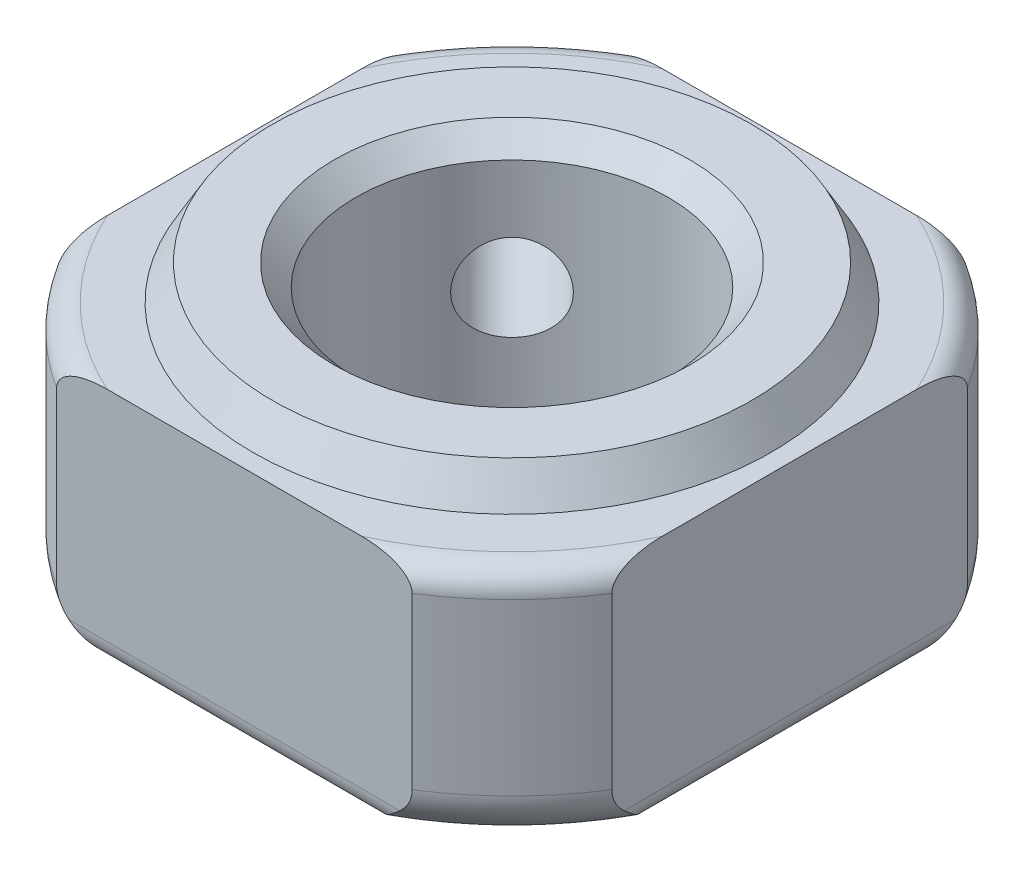
SolidWorks part; units mm, degrees
ref_plane "Front" through (0, 0, 0) normal (0, 0, 1) x (1, 0, 0)
ref_plane "Top" through (0, 0, 0) normal (0, 1, 0) x (1, 0, 0)
ref_plane "Right" through (0, 0, 0) normal (1, 0, 0) x (0, 0, -1)
sketch "Sketch1" plane through (0, 0, 0) normal (0, 1, 0) x (1, 0, 0)
  line L0 (-8, 5.1235) -> (-8, -5.1235)
  line L1 (-8, 8) -> (8, 8) construction
  line L2 (-8, 8) -> (-8, -8) construction
  line L3 (-8, -8) -> (8, -8) construction
  line L4 (8, 8) -> (8, -8) construction
  line L5 (-8, 8) -> (8, -8) construction
  line L6 (-8, -8) -> (8, 8) construction
  line L7 (-5.1235, -8) -> (5.1235, -8)
  line L8 (8, -5.1235) -> (8, 5.1235)
  line L9 (5.1235, 8) -> (-5.1235, 8)
  arc A0 (-5.1235, 8) -> (-8, 5.1235) centre (0, 0) ccw
  arc A1 (8, 5.1235) -> (5.1235, 8) centre (0, 0) ccw
  arc A2 (5.1235, -8) -> (8, -5.1235) centre (0, 0) ccw
  arc A3 (-8, -5.1235) -> (-5.1235, -8) centre (0, 0) ccw
  point P0 (0, 0)
  dimension "D2" = 19
  dimension "D1" = 16
extrude "Boss-Extrude1" add sketch "Sketch1" along normal blind 8
sketch "Sketch2" plane through (0, 0, 0) normal (0, 0, 1) x (1, 0, 0)
  line L0 (6.9, 8) -> (7.4774, 7)
  line L1 (-5.1235, 8) -> (5.1235, 8) construction
  line L2 (7.4774, 7) -> (9.7567, 7)
  line L4 (6.9, 8) -> (9.7567, 8)
  line L5 (9.7567, 8) -> (9.7567, 7)
  line L6 (0, 0) -> (0, 12.5902) construction
  dimension "D1" = 1
  dimension "D2" = 60
  dimension "D3" = 6.9
revolve "Cut-Revolve1" cut sketch "Sketch2" angle 360 about L6
hole_wizard "M10x1.0 Tapped Hole1" positions "Sketch3" profile "Sketch5" tap size "M10x1.0" standard "ISO" end condition up to next
sketch "Sketch3" plane through (0, 0, 0) normal (0, -1, 0) x (-1, 0, 0)
  point P0 (0, 0)
sketch "Sketch5" plane through (0, 0, 0) normal (1, 0, 0) x (0, 0, -1)
  line L0 (0, 0) -> (0, 8)
  line L1 (0, 8) -> (5.125, 8)
  line L2 (4.5, 7.375) -> (4.5, 0.625)
  line L3 (4.5, 0.625) -> (5.125, 0)
  line L5 (5.125, 0) -> (0, 0)
  line L6 (-4.5, 0.625) -> (-5.125, 0) construction
  line L7 (5.125, 8) -> (4.5, 7.375)
  line L8 (-5.125, 8) -> (-4.5, 7.375) construction
  line L11 (0, -6.35) -> (0, 107.95) construction
  dimension "Thru Tap Drill Dia." = 9
  dimension "Thru Tap Drill Depth" = 8
  dimension "Near C'Sink Dia." = 10.25
  dimension "Near C'Sink Angle" = 90
  dimension "Far C'Sink Dia." = 10.25
  dimension "Far C'Sink Angle" = 90
cosmetic thread "Hole Thread1" parameters "D2"=10
ref_plane "Plane1" through (-6.7175, 7, -6.7175) normal (-0.7071, 0, -0.7071) x (-0.7071, 0, 0.7071)
hole_wizard "M3 Tapped Hole1" positions "Sketch7" profile "Sketch9" tap size "M3" standard "ISO" end condition up to next
sketch "Sketch7" plane through (-6.7175, 7, -6.7175) normal (-0.7071, 0, -0.7071) x (-0.7071, 0, 0.7071)
  point P0 (0, -2.8049)
sketch "Sketch9" plane through (-6.7175, 4.1951, -6.7175) normal (0, 1, 0) x (-0.7071, 0, 0.7071)
  line L0 (0, 0) -> (0, 5)
  line L1 (0, 5) -> (1.25, 5)
  line L2 (1.25, 5) -> (1.25, 0.275)
  line L3 (1.25, 0.275) -> (1.525, 0)
  line L5 (1.525, 0) -> (0, 0)
  line L6 (-1.25, 0.275) -> (-1.525, 0) construction
  line L11 (0, -6.35) -> (0, 107.95) construction
  dimension "Thru Tap Drill Dia." = 2.5
  dimension "Thru Tap Drill Depth" = 5
  dimension "Near C'Sink Dia." = 3.05
  dimension "Near C'Sink Angle" = 90
cosmetic thread "Hole Thread2" parameters "D2"=3
fillet "Fillet2" radius 1.4 4 edges at (6.7175, 0, -6.7175) (6.7175, 0, 6.7175) (-6.7175, 0, 6.7175) (-6.7175, 0, -6.7175)
fillet "Fillet3" radius 0.7 8 edges at (-6.7175, 7, 6.7175) (-6.7175, 7, -6.7175) (6.7175, 7, -6.7175) (6.7175, 7, 6.7175) (8, 0, 0) (0, 0, 8) (0, 0, -8) (-8, 0, 0) tangent propagation no
